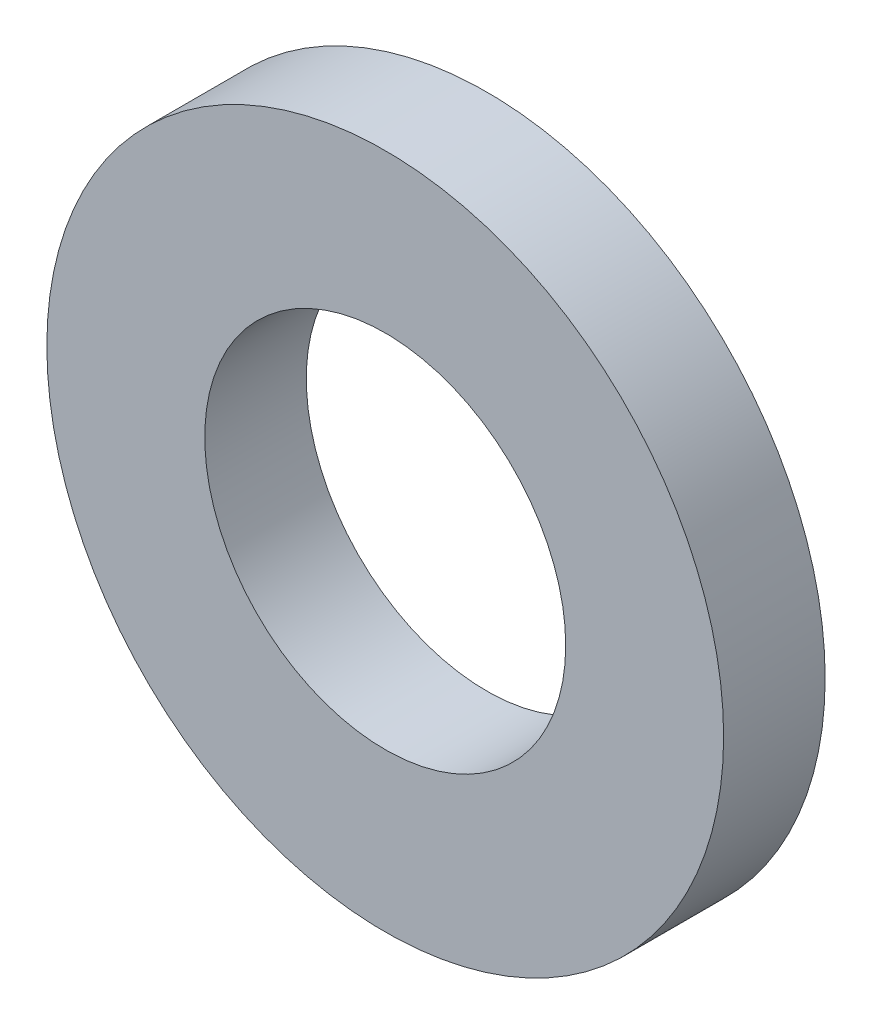
SolidWorks part; units mm, degrees
ref_plane "Front Plane" through (0, 0, 0) normal (0, 0, 1) x (1, 0, 0)
ref_plane "Top Plane" through (0, 0, 0) normal (0, 1, 0) x (1, 0, 0)
ref_plane "Right Plane" through (0, 0, 0) normal (1, 0, 0) x (0, 0, -1)
sketch "Sketch1" plane through (0, 0, 0) normal (0, 0, 1) x (1, 0, 0)
  circle A0 centre (0, 0) radius 6
  circle A1 centre (0, 0) radius 3.2
  dimension "OD" = 12
  dimension "ID1" = 6.4
extrude "Boss-Extrude1" add sketch "Sketch1" along normal blind 1.8
ref_axis "Axis1" through (0, 0, 1.8) along (0, 0, -1)
